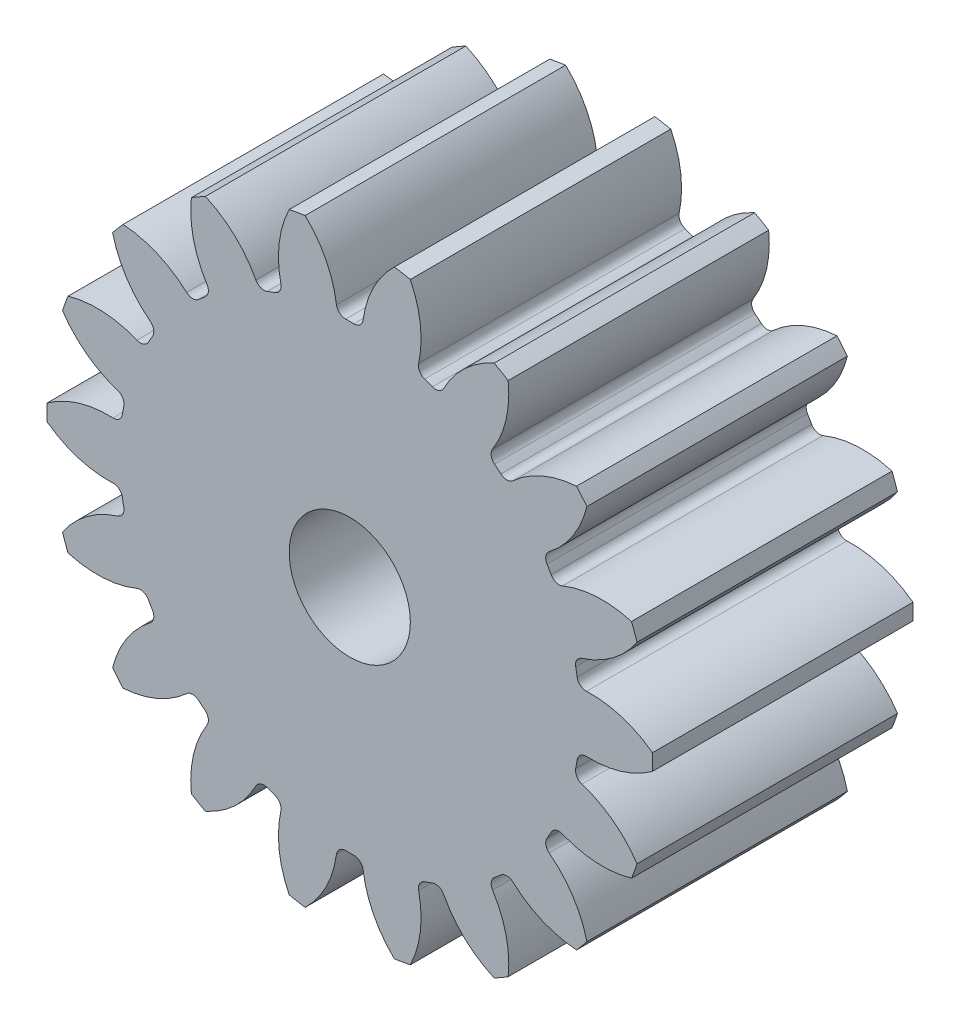
SolidWorks part; units mm, degrees
ref_plane "Front Plane" through (0, 0, 0) normal (0, 0, 1) x (1, 0, 0)
ref_plane "Top Plane" through (0, 0, 0) normal (0, 1, 0) x (1, 0, 0)
ref_plane "Right Plane" through (0, 0, 0) normal (1, 0, 0) x (0, 0, -1)
sketch "Sketch1" plane through (0, 0, 0) normal (0, 0, 1) x (1, 0, 0)
  circle A0 centre (0, 0) radius 4.5
  circle A1 centre (0, 0) radius 5
  circle A2 centre (0, 0) radius 3.8
  dimension "D1" = 9
  dimension "D2" = 0.5
  dimension "D3" = 1.2
extrude "Boss-Extrude1" add sketch "Sketch1" along normal mid plane 4.3 contours A1
sketch "Gear Profile" plane through (0, 0, 0) normal (0, 0, 1) x (1, 0, 0)
  line L0 (0, 0) -> (0, 5) construction
  line L1 (-0.3922, 4.4829) -> (0.3922, 4.4829) construction
  line L2 (-0.2069, 3.7944) -> (0, 0) construction
  line L3 (0, 3.7131) -> (-0.8748, 5.43) construction
  line L4 (0, 0) -> (0.8682, 4.924) construction
  line L5 (0.3922, 4.4829) -> (1.1647, 4.3467) construction
  circle A0 centre (0, 0) radius 5 construction
  arc A1 (-1.3626, 5.3285) -> (-0.2069, 3.7944) centre (-1.9277, 3.7005) cw
  arc A2 (1.3626, 5.3285) -> (0.2069, 3.7944) centre (1.9277, 3.7005) ccw
  circle A3 centre (0, 0) radius 3.8 construction
  arc A4 (0.2069, 3.7944) -> (-0.2069, 3.7944) centre (0, 0) ccw
  circle A5 centre (0, 0) radius 4.5 construction
  circle A6 centre (0, 0) radius 5 construction
  circle A7 centre (0, 0) radius 5.5
  arc A8 (1.3626, 5.3285) -> (-1.3626, 5.3285) centre (0, 0) ccw
  dimension "D2" = 27
  dimension "D3" = 10
  dimension "D1" = 0.5
extrude "Cut-Extrude1" cut sketch "Gear Profile" against normal through all both and the other way through all
fillet "Fillet1" radius 0.15 2 edges at (0.2069, 3.7944, 0) (-0.2069, 3.7944, 0)
ref_axis "Axis1" through (0, 0, -2.75) along (0, 0, 1)
pattern_circular "CirPattern1" count 18 over 360 about axis through (0, 0, -2.75) along (0, 0, 1) of "Fillet1", "Cut-Extrude1"
sketch "Sketch2" plane through (0, 0, 0) normal (0, 0, 1) x (1, 0, 0)
  circle A0 centre (0, 0) radius 1
  dimension "D1" = 2
extrude "Cut-Extrude2" cut sketch "Sketch2" against normal through all both and the other way through all
sketch "Sketch3" plane through (0, 0, 0) normal (0, 0, 1) x (1, 0, 0)
  point P0 (0, 0)
equation "\"Module\"= 0.5mm"
equation "\"Number of Teeth\"= 18"
equation "\"D1@Sketch1\"=\"Module\" * \"Number of Teeth\""
equation "\"D2@Sketch1\"=\"Module\""
equation "\"D3@Sketch1\"=\"Module\" * if( \"Module\"=>1.25,2.25,2.4)"
equation "\"Width\"= 4.3mm"
equation "\"D1@Boss-Extrude1\"=\"Width\""
equation "\"Pressure Angle\"= 27deg"
equation "\"D2@Gear Profile\"=\"Pressure Angle\""
equation "\"D3@Gear Profile\"=180 / \"Number of Teeth\""
equation "\"D1@Fillet1\"=0.3*\"Module\""
equation "\"D1@CirPattern1\"=\"Number of Teeth\""
equation "\"Hole Diammeter\"= 2"
equation "\"D1@Sketch2\"=\"Hole Diammeter\""
